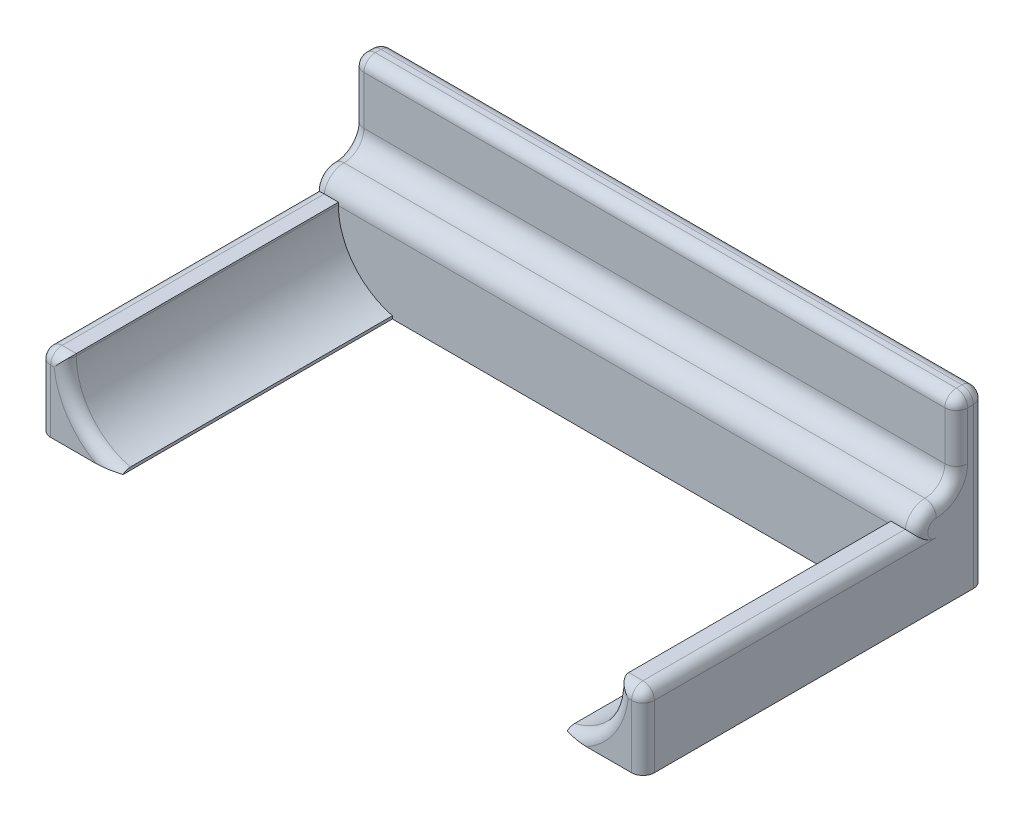
SolidWorks part; units mm, degrees
ref_plane "Plan de face" through (0, 0, 0) normal (0, 0, 1) x (1, 0, 0)
ref_plane "Plan de dessus" through (0, 0, 0) normal (0, 1, 0) x (1, 0, 0)
ref_plane "Plan de droite" through (0, 0, 0) normal (1, 0, 0) x (0, 0, -1)
sketch "Esquisse1" plane through (0, 0, 0) normal (0, 0, 1) x (1, 0, 0)
  line L1 (0, 0) -> (53, 0)
  line L2 (0, 0) -> (0, 20)
  line L3 (0, 20) -> (53, 20)
  line L4 (53, 0) -> (53, 20)
  point P4 (0, 0)
  point P5 (0, 0)
  point P6 (0, 0)
  point P7 (0, 0)
extrude "Boss.-Extru.1" add sketch "Esquisse1" along normal blind 30
sketch "Esquisse2" plane through (0, 20, 0) normal (0, 1, 0) x (1, 0, 0)
  line L0 (53, -30) -> (0, -30) construction
  line L1 (0, -2.5) -> (53, -2.5)
  line L2 (0, -2.5) -> (0, -30)
  line L3 (0, -30) -> (53, -30)
  line L4 (53, -2.5) -> (53, -30)
  line L5 (0, -30) -> (0, 0) construction
  line L6 (53, -30) -> (53, 0) construction
  line L7 (53, 0) -> (0, 0) construction
  dimension "D1" = 0
  dimension "D2" = 0
  dimension "D3" = 0
  dimension "D4" = 2.5
extrude "Enlèv. mat.-Extru.1" cut sketch "Esquisse2" against normal blind 17.5
sketch "Esquisse8" plane through (0, 0, 0) normal (0, 0, -1) x (-1, 0, 0)
  line L0 (-53, 0) -> (-53, 20) construction
  line L1 (-53, 20) -> (0, 20)
  line L2 (-53, 20) -> (-53, 15)
  line L3 (-53, 15) -> (0, 15)
  line L4 (0, 20) -> (0, 15)
  line L5 (0, 20) -> (0, 0) construction
  line L6 (-53, 20) -> (0, 20) construction
  dimension "D1" = 0
  dimension "D2" = 0
  dimension "D3" = 0
  dimension "D4" = 5
extrude "Enlèv. mat.-Extru.5" cut sketch "Esquisse8" against normal through all
sketch "Esquisse10" plane through (0, 2.5, 0) normal (0, 1, 0) x (1, 0, 0)
  line L0 (0, -2.5) -> (0, -30) construction
  line L1 (7, -6) -> (46, -6)
  line L2 (7, -6) -> (7, -30)
  line L3 (7, -30) -> (46, -30)
  line L4 (46, -6) -> (46, -30)
  line L5 (53, -30) -> (53, -2.5) construction
  line L6 (0, -30) -> (53, -30) construction
  line L7 (53, 0) -> (0, 0) construction
  dimension "D1" = 7
  dimension "D2" = 7
  dimension "D3" = 0
  dimension "D4" = 6
extrude "Enlèv. mat.-Extru.6" cut sketch "Esquisse10" against normal blind 3
sketch "Esquisse11" plane through (0, 2.5, 0) normal (0, 1, 0) x (1, 0, 0)
  line L0 (0, -2.5) -> (0, -30) construction
  line L1 (0, -2.5) -> (53, -2.5)
  line L2 (0, -2.5) -> (0, -6)
  line L3 (0, -6) -> (53, -6)
  line L4 (53, -2.5) -> (53, -6)
  line L5 (53, -30) -> (53, -2.5) construction
  line L6 (46, -6) -> (7, -6) construction
  line L7 (53, -2.5) -> (0, -2.5) construction
  point P4 (27.0628, -3.6594)
  dimension "D1" = 0
  dimension "D2" = 0
  dimension "D3" = 0
  dimension "D4" = 0
extrude "Boss.-Extru.3" add sketch "Esquisse11" along normal blind 5.5
sketch "Esquisse12" plane through (0, 2.5, 0) normal (0, 1, 0) x (1, 0, 0)
  line L0 (0, -6) -> (0, -30) construction
  line L1 (2.25, -6) -> (7, -6)
  line L2 (2.25, -6) -> (2.25, -30)
  line L3 (2.25, -30) -> (7, -30)
  line L4 (7, -6) -> (7, -30)
  line L5 (7, -6) -> (7, -30) construction
  line L6 (0, -30) -> (7, -30) construction
  line L7 (0, -6) -> (7, -6) construction
  line L8 (46, -6) -> (53, -6) construction
  line L9 (46, -6) -> (50.75, -6)
  line L10 (46, -6) -> (46, -30)
  line L11 (46, -30) -> (50.75, -30)
  line L12 (50.75, -6) -> (50.75, -30)
  line L13 (46, -30) -> (53, -30) construction
  line L14 (53, -30) -> (53, -6) construction
  line L15 (46, -30) -> (46, -6) construction
  point P12 (3.5, -6)
  point P17 (13.5554, -4.5036)
  dimension "D1" = 2.25
  dimension "D2" = 0
  dimension "D3" = 0
  dimension "D4" = 0
  dimension "D5" = 0
  dimension "D6" = 0
  dimension "D7" = 2.25
  dimension "D8" = 0
extrude "Enlèv. mat.-Extru.7" cut sketch "Esquisse12" against normal blind 2.25
sketch "Esquisse13" plane through (0, 2.5, 0) normal (0, 1, 0) x (1, 0, 0)
  line L0 (0, -6) -> (2.25, -6) construction
  line L1 (0, -6) -> (2.25, -6)
  line L2 (0, -6) -> (0, -30)
  line L3 (0, -30) -> (2.25, -30)
  line L4 (2.25, -6) -> (2.25, -30)
  line L5 (50.75, -6) -> (53, -6)
  line L6 (50.75, -6) -> (50.75, -30)
  line L7 (50.75, -30) -> (53, -30)
  line L8 (53, -6) -> (53, -30)
  line L9 (50.75, -6) -> (53, -6) construction
  line L10 (0, -6) -> (0, -30) construction
  line L11 (2.25, -6) -> (2.25, -30) construction
  line L12 (0, -30) -> (2.25, -30) construction
  line L13 (53, -30) -> (53, -6) construction
  line L14 (50.75, -30) -> (50.75, -6) construction
  line L15 (50.75, -30) -> (53, -30) construction
  dimension "D1" = 0
  dimension "D2" = 0
  dimension "D3" = 0
  dimension "D4" = 0
  dimension "D5" = 0
  dimension "D6" = 0
  dimension "D7" = 0
  dimension "D8" = 0
extrude "Boss.-Extru.4" add sketch "Esquisse13" along normal blind 4
fillet "Congé14" radius 1.75 2 edges at (26.5, 8, 6) (26.5, 8, 2.5)
fillet "Congé16" radius 6.25 2 edges at (2.25, 0.25, 18) (50.75, 0.25, 18)
fillet "Congé17" radius 1 20 edges at (0, 7.5729, 5.3956) (0, 8.5126, 3.0126) (53, 12.375, 2.5) (53, 8.5126, 3.0126) (0, 12.375, 2.5) (53, 15, 1.25) (0, 15, 1.25) (0, 7.5, 0) (26.5, 15, 0) (26.5, 15, 2.5) (53, 7.5, 0) (53, 7.5729, 5.3956) (0, 6.5, 17.991) (53, 6.5, 17.991) (53, 3.25, 30) (49.4213, 2.4646, 30) (51.875, 6.5, 30) (0, 3.25, 30) (1.125, 6.5, 30) (3.5787, 2.4646, 30)
